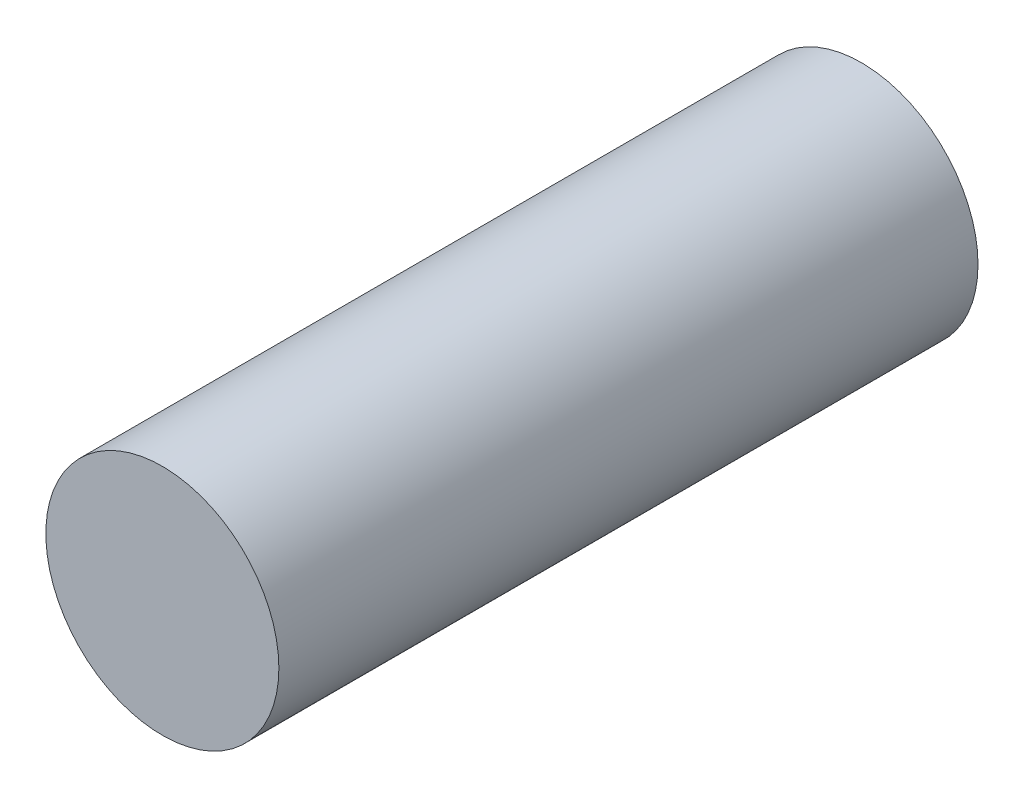
SolidWorks part; units mm, degrees
ref_plane "Płaszczyzna przednia" through (0, 0, 0) normal (0, 0, 1) x (1, 0, 0)
ref_plane "Płaszczyzna górna" through (0, 0, 0) normal (0, 1, 0) x (1, 0, 0)
ref_plane "Płaszczyzna prawa" through (0, 0, 0) normal (1, 0, 0) x (0, 0, -1)
sketch "Sketch1" plane through (0, 0, 0) normal (0, 0, 1) x (1, 0, 0)
  circle A0 centre (0, 0) radius 5
  dimension "D1" = 10
extrude "Boss-Extrude1" add sketch "Sketch1" along normal blind 30
